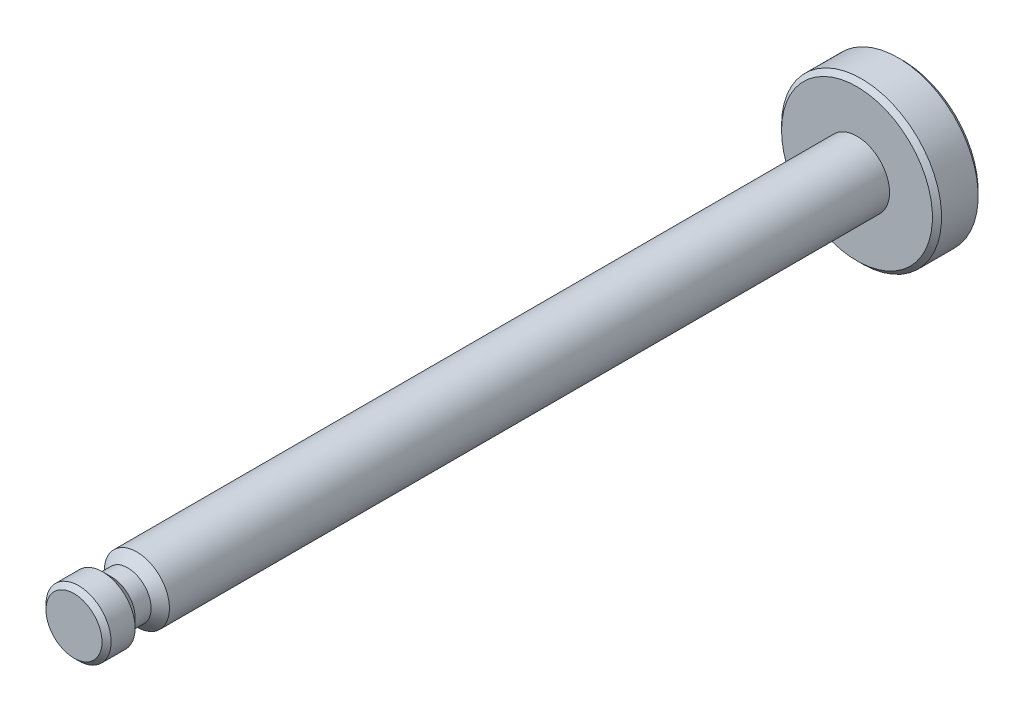
SolidWorks part; units mm, degrees
ref_plane "Front" through (0, 0, 0) normal (0, 0, 1) x (1, 0, 0)
ref_plane "Top" through (0, 0, 0) normal (0, 1, 0) x (1, 0, 0)
ref_plane "Right" through (0, 0, 0) normal (1, 0, 0) x (0, 0, -1)
sketch "Sketch2" plane through (0, 0, 0) normal (0, 0, 1) x (1, 0, 0)
  circle A0 centre (0, 0) radius 1.425
  dimension "D1" = 2.85
extrude "Shaft" add sketch "Sketch2" along normal blind 34.25
sketch "Sketch3" plane through (0, 0, 0) normal (0, 0, -1) x (-1, 0, 0)
  circle A3 centre (0, 0) radius 3.5
  dimension "D1" = 7
extrude "Head" add sketch "Sketch3" along normal blind 2
sketch "Sketch4" plane through (0, 0, 0) normal (1, 0, 0) x (0, 0, -1)
  line L0 (0, 0) -> (-32.25, 0) construction
  line L1 (-32.25, 0) -> (-32.25, 4.3666) construction
  line L2 (-33, 1.425) -> (-31.5, 1.425)
  line L3 (0, 1.425) -> (-34.25, 1.425) construction
  line L6 (-31.5, 1.425) -> (-31.9, 1.025)
  line L7 (-31.9, 1.025) -> (-32.6, 1.025)
  line L8 (-32.6, 1.025) -> (-33, 1.425)
  dimension "D1" = 32.25
  dimension "D2" = 1.5
  dimension "D3" = 45
  dimension "D4" = 0.4
revolve "e-Clip Notch" cut sketch "Sketch4" angle 360 about L0
chamfer "Deburs" distance 0.2 angle 45 3 edges at (1.425, 0, 34.25) (-3.5, 0, 0) (-3.5, 0, -2)
equation "\"D1@Sketch2\"=\"Hardware Clearance Hole Diameter@Box Assy.Assembly\"-.3"
